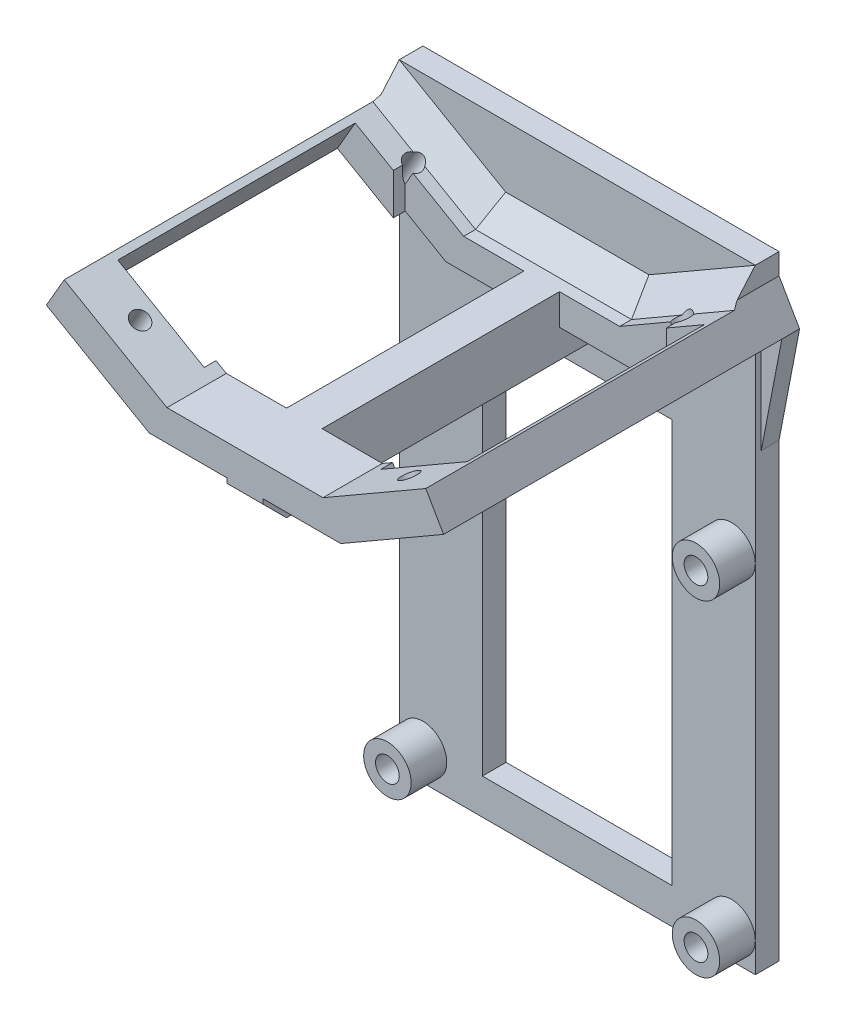
SolidWorks part; units mm, degrees
ref_plane "前基準面" through (0, 0, 0) normal (0, 0, 1) x (1, 0, 0)
ref_plane "上基準面" through (0, 0, 0) normal (0, 1, 0) x (1, 0, 0)
ref_plane "右基準面" through (0, 0, 0) normal (1, 0, 0) x (0, 0, -1)
sketch "草圖1" plane through (0, 0, 0) normal (0, 0, 1) x (1, 0, 0)
  line L0 (-15, 0) -> (15, 0)
  line L1 (-15, 0) -> (-15, -15)
  line L2 (16.7321, -18) -> (15, -19)
  line L3 (15, -19) -> (15, -65)
  line L4 (15, -65) -> (-15, -65)
  line L5 (-15, -65) -> (-15, -19)
  line L6 (-15, -19) -> (-16.7321, -18)
  line L7 (-15, -15) -> (-16.7321, -18)
  line L8 (0, 15.1551) -> (0, -26.7536) construction
  line L9 (15, 0) -> (15, -15)
  line L10 (15, -15) -> (16.7321, -18)
  dimension "D7" = 60
  dimension "D8" = 2
  dimension "D9" = 15
  dimension "D10" = 15
  dimension "D1" = 30
  dimension "D2" = 15
  dimension "D3" = 30
  dimension "D4" = 15
  dimension "D5" = 65
  dimension "D6" = 120
  dimension "D11" = 90
extrude "填料-伸長1" add sketch "草圖1" along normal blind 2
sketch "草圖2" plane through (0, 0, 2) normal (0, 0, 1) x (1, 0, 0)
  line L0 (0, 35.4377) -> (0, -39.094) construction
  line L2 (-16.7321, -18) -> (-8.0718, -23)
  line L3 (-8.0718, -23) -> (8.0718, -23)
  line L4 (8.0718, -23) -> (16.7321, -18)
  line L5 (15, -19) -> (16.7321, -18) construction
  line L6 (-16.7321, -18) -> (-15, -19) construction
  line L7 (-16.7321, -18) -> (-15.2321, -15.4019)
  line L8 (-15, -15) -> (-16.7321, -18) construction
  line L9 (-15.2321, -15.4019) -> (-6.5718, -20.4019)
  line L10 (-6.5718, -20.4019) -> (6.5718, -20.4019)
  line L11 (6.5718, -20.4019) -> (15.2321, -15.4019)
  line L12 (16.7321, -18) -> (15, -15) construction
  line L13 (15.2321, -15.4019) -> (16.7321, -18)
  dimension "D1" = 10
  dimension "D2" = 3
  dimension "D3" = 3
  dimension "D4" = 10
  dimension "D5" = 10
extrude "填料-伸長2" add sketch "草圖2" along normal blind 28 and the other way blind 2
sketch "草圖3" plane through (10.8131, -21.4173, 0) normal (-0.5, 0.866, 0) x (0.866, 0.5, 0)
  line L1 (6.8346, -30) -> (-3.1654, -30) construction
  line L2 (6.8346, -2) -> (6.8346, -30) construction
  line L5 (6.8346, -6) -> (-2.1654, -6)
  line L6 (6.8346, -6) -> (6.8346, -26)
  line L7 (6.8346, -26) -> (-2.1654, -26)
  line L8 (-2.1654, -6) -> (-2.1654, -26)
  circle A2 centre (2.3346, -4.5) radius 0.75
  circle A3 centre (2.3346, -27.5) radius 0.75
  dimension "D7" = 1.5
  dimension "D2" = 20
  dimension "D3" = 9
  dimension "D4" = 23
  dimension "D5" = 1.5
  dimension "D6" = 4
  dimension "D11" = 4.5
extrude "除料-伸長5" cut sketch "草圖3" along normal up to next
sketch "草圖12" plane through (-11.9772, -20.7452, 0) normal (-0.5, -0.866, 0) x (0.866, -0.5, 0)
  line L0 (-5.4904, 30) -> (-5.4904, 0) construction
  line L1 (-5.4904, 26) -> (3.5096, 26)
  line L2 (-5.4904, 26) -> (-5.4904, 6)
  line L3 (-5.4904, 6) -> (3.5096, 6)
  line L4 (3.5096, 26) -> (3.5096, 6)
  line L5 (-5.4904, 30) -> (4.5096, 30) construction
  circle A0 centre (-0.9904, 27.5) radius 0.75
  circle A1 centre (-0.9904, 4.5) radius 0.75
  dimension "D7" = 1.5
  dimension "D8" = 1.5
  dimension "D1" = 9
  dimension "D2" = 20
  dimension "D3" = 4
  dimension "D4" = 23
  dimension "D5" = 1.5
  dimension "D6" = 4.5
extrude "除料-伸長7" cut sketch "草圖12" against normal up to next
sketch "草圖13" plane through (0, 0, 2) normal (0, 0, 1) x (1, 0, 0)
  line L1 (-15, -65) -> (15, -65) construction
  line L2 (-8.0718, -23) -> (8.0718, -23) construction
  line L3 (-8, -28) -> (8, -28)
  line L4 (-8, -28) -> (-8, -62)
  line L5 (-8, -62) -> (8, -62)
  line L6 (8, -28) -> (8, -62)
  line L7 (-8, -28) -> (8, -62) construction
  line L8 (-8, -62) -> (8, -28) construction
  circle A0 centre (-13, -35) radius 1
  circle A1 centre (13, -35) radius 1
  circle A2 centre (-13, -62.5) radius 1
  circle A3 centre (13, -62.5) radius 1
  point P11 (0, -45)
  dimension "D4" = 2
  dimension "D5" = 2
  dimension "D6" = 2
  dimension "D7" = 2
  dimension "D1" = 26
  dimension "D2" = 27.5
  dimension "D3" = 2.5
  dimension "D8" = 13
  dimension "D9" = 16
  dimension "D10" = 3
  dimension "D11" = 5
extrude "除料-伸長8" cut sketch "草圖13" against normal up to next
chamfer "導角5" distance 2 angle 45 3 edges at (10.9019, -17.9019, 2) (0, -20.4019, 2) (-10.9019, -17.9019, 2)
sketch "草圖14" plane through (0, 0, 30) normal (0, 0, 1) x (1, 0, 0)
  line L0 (6.5718, -20.4019) -> (-6.5718, -20.4019) construction
  line L1 (-1.5, -25.4019) -> (1.5, -25.4019)
  line L2 (-1.5, -25.4019) -> (-1.5, -20.4019)
  line L3 (-1.5, -20.4019) -> (1.5, -20.4019)
  line L4 (1.5, -25.4019) -> (1.5, -20.4019)
  line L5 (-1.5, -25.4019) -> (1.5, -20.4019) construction
  line L6 (-1.5, -20.4019) -> (1.5, -25.4019) construction
  point P0 (0, -22.9019)
  dimension "D1" = 5
  dimension "D2" = 3
extrude "填料-伸長8" add sketch "草圖14" against normal up to surface (28 mm away) up to face at (0, -45, 2)
chamfer "導角6" distance 2 angle 45 1 edges at (0, -25.4019, 30)
sketch "草圖15" plane through (0, 0, 2) normal (0, 0, 1) x (1, 0, 0)
  circle A0 centre (-13, -35) radius 1
  circle A1 centre (-13, -35) radius 2
  circle A2 centre (13, -35) radius 1
  circle A3 centre (13, -35) radius 2
  circle A4 centre (13, -62.5) radius 1
  circle A5 centre (13, -62.5) radius 2
  circle A6 centre (-13, -62.5) radius 1
  circle A7 centre (-13, -62.5) radius 2
extrude "填料-伸長9" add sketch "草圖15" along normal blind 3
sketch "草圖16" plane through (0, -23, 0) normal (0, -1, 0) x (1, 0, 0)
  line L0 (-1.5, 2) -> (-1.5, 28) construction
  line L1 (-1.5, 25) -> (-11.5, 25)
  line L2 (-1.5, 25) -> (-1.5, 5)
  line L3 (-1.5, 5) -> (-11.5, 5)
  line L4 (-11.5, 25) -> (-11.5, 5)
  line L5 (1.5, 2) -> (1.5, 30) construction
  line L6 (1.5, 25) -> (11.5, 25)
  line L7 (1.5, 25) -> (1.5, 5)
  line L8 (1.5, 5) -> (11.5, 5)
  line L9 (11.5, 25) -> (11.5, 5)
  dimension "D1" = 10
  dimension "D2" = 10
  dimension "D3" = 20
  dimension "D4" = 20
  dimension "D5" = 5
  dimension "D6" = 5
extrude "除料-伸長9" cut sketch "草圖16" against normal up to next
sketch "草圖17" plane through (0, 0, 30) normal (0, 0, 1) x (1, 0, 0)
  line L0 (-15.2321, -15.4019) -> (-16.7321, -18)
  line L1 (-16.7321, -18) -> (-16.2124, -18.3)
  line L3 (-16.7321, -18) -> (-8.0718, -23) construction
  line L5 (-16.2124, -18.3) -> (-14.7124, -15.7019)
  line L6 (-6.5718, -20.4019) -> (-15.2321, -15.4019) construction
  line L7 (15.2321, -15.4019) -> (16.7321, -18)
  line L8 (16.7321, -18) -> (16.2124, -18.3)
  line L9 (8.0718, -23) -> (16.7321, -18) construction
  line L10 (16.2124, -18.3) -> (14.7124, -15.7019)
  line L11 (15.2321, -15.4019) -> (11.8191, -17.3724) construction
  line L12 (14.7124, -15.7019) -> (15.2321, -15.4019)
  line L13 (-14.7124, -15.7019) -> (-15.2321, -15.4019)
  dimension "D1" = 0.6
  dimension "D2" = 0.6
extrude "填料-伸長10" add sketch "草圖17" against normal up to surface (24 mm away) up to face at (13.741, -17.9948, 6)
sketch "草圖18" plane through (0, 0, 0) normal (0, 0, -1) x (-1, 0, 0)
  line L0 (-16.7321, -18) -> (-15, -27)
  line L1 (-15, -19) -> (-15, -27)
  line L2 (-15, -65) -> (-15, -19) construction
  line L3 (-16.7321, -18) -> (-15, -19)
  line L4 (16.7321, -18) -> (15, -19)
  line L5 (15, -19) -> (15, -27)
  line L6 (15, -19) -> (15, -65) construction
  line L7 (15, -27) -> (16.7321, -18)
  dimension "D1" = 8
extrude "填料-伸長11" add sketch "草圖18" against normal blind 1.5
sketch "草圖19" plane through (0, 0, 2) normal (0, 0, 1) x (1, 0, 0)
  line L1 (-15, -13.2265) -> (15, -13.2265)
  line L2 (-15, -13.2265) -> (-15, 0)
  line L3 (-15, 0) -> (15, 0)
  line L4 (15, -13.2265) -> (15, 0)
extrude "除料-伸長10" cut sketch "草圖19" against normal up to next
